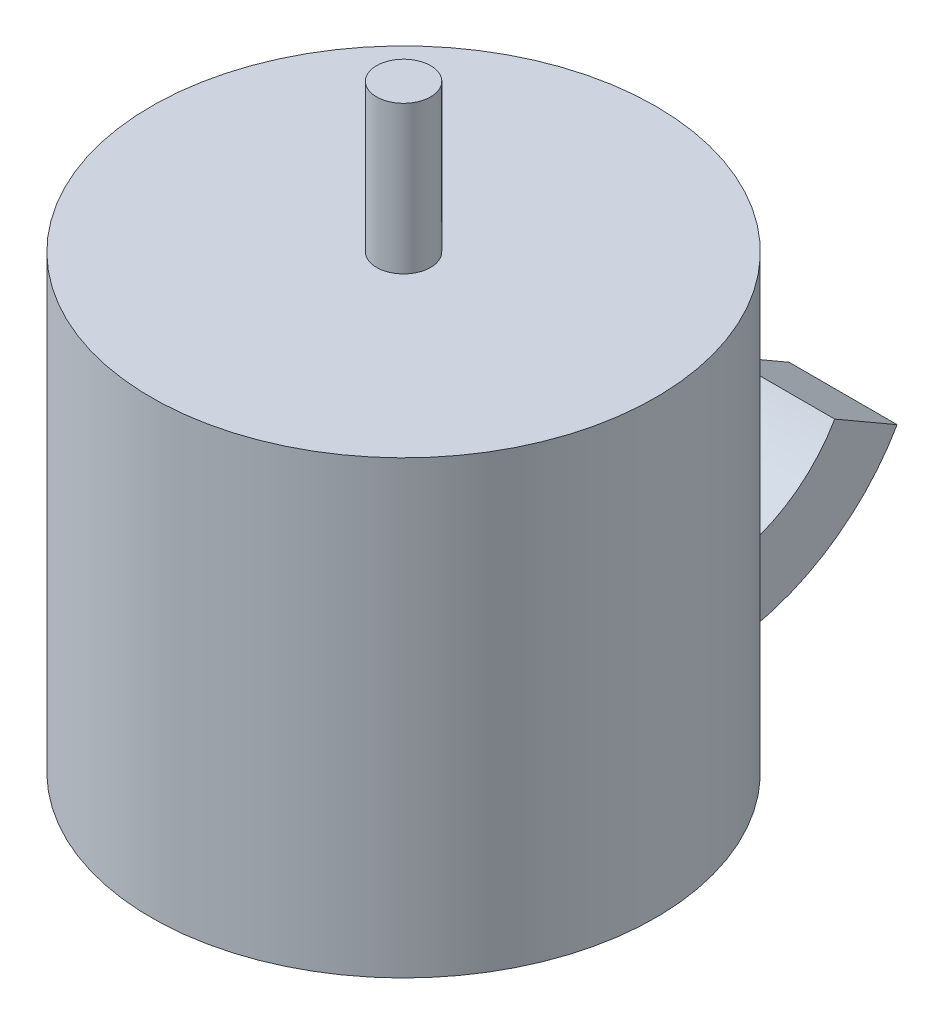
SolidWorks part; units mm, degrees
ref_plane "Front Plane" through (0, 0, 0) normal (0, 0, 1) x (1, 0, 0)
ref_plane "Top Plane" through (0, 0, 0) normal (0, 1, 0) x (1, 0, 0)
ref_plane "Right Plane" through (0, 0, 0) normal (1, 0, 0) x (0, 0, -1)
sketch "Sketch1" plane through (0, 0, 0) normal (0, 0, 1) x (1, 0, 0)
  line L0 (0, -74.46) -> (0, 71.5861) construction
  line L1 (-0.75, 0) -> (-7, 0)
  line L2 (55, 0) -> (-55, 0) construction
  line L3 (-7, 0) -> (-7, 12.5)
  line L4 (-7, 12.5) -> (-0.75, 12.5)
  line L5 (0, -0.9) -> (0, 16.6)
  line L6 (-0.75, 0) -> (-0.75, -0.9)
  line L7 (-0.75, 12.5) -> (-0.75, 16.6)
  line L8 (-0.75, 16.6) -> (0, 16.6)
  line L9 (-0.75, -0.9) -> (0, -0.9)
  dimension "D1" = 7
  dimension "D2" = 0.75
  dimension "D3" = 12.5
  dimension "D4" = 4.1
  dimension "D5" = 17.5
revolve "Revolve1" add sketch "Sketch1" angle 360 about L0
hole_wizard "M2x0.4 Tapped Hole1" positions "Sketch2" profile "Sketch3" tap size "M2x0.4" standard "ANSI Metric"
sketch "Sketch2" plane through (0, 0, 0) normal (0, -1, 0) x (-1, 0, 0)
  line L1 (-3.182, -3.182) -> (0, 0) construction
  line L2 (0, 0) -> (0, -2.9249) construction
  circle A0 centre (0, 0) radius 4.5
  point P0 (3.182, -3.182)
  point P11 (-3.182, -3.182)
  point P12 (-3.182, 3.182)
  point P13 (3.182, 3.182)
  dimension "D2" = 9
  dimension "D3" = 45
  dimension "D1" = 4
sketch "Sketch3" plane through (-3.182, 0, 3.182) normal (1, 0, 0) x (0, 0, -1)
  line L0 (0, 0) -> (0, 5.6807)
  line L1 (0, 5.6807) -> (0.8, 5.2)
  line L2 (0.8, 5.2) -> (0.8, 0)
  line L5 (0.8, 0) -> (0, 0)
  line L10 (0, 5.6807) -> (-0.8, 5.2) construction
  line L11 (0, -6.35) -> (0, 107.95) construction
  dimension "Tap Drill Dia." = 1.6
  dimension "Tap Drill Depth" = 5.2
  dimension "Drill Angle" = 118
cosmetic thread "Hole Thread1" parameters "D1"=4, "D2"=2
cosmetic thread "Hole Thread3" parameters "D1"=4, "D2"=2
cosmetic thread "Hole Thread4" parameters "D1"=4, "D2"=2
cosmetic thread "Hole Thread5" parameters "D1"=4, "D2"=2
ref_plane "Plane1" through (0, 0, -7) normal (0, 0, -1) x (-1, 0, 0)
sketch "Sketch4" plane through (0, 0, -7) normal (0, 0, -1) x (-1, 0, 0)
  line L1 (1.5, 0) -> (-1.5, 0)
  line L2 (1.5, 0) -> (1.5, 2)
  line L3 (1.5, 2) -> (-1.5, 2)
  line L4 (-1.5, 0) -> (-1.5, 2)
  point P4 (0, 0)
  dimension "D1" = 3
  dimension "D2" = 2
extrude "Boss-Extrude1" [suppressed] add sketch "Sketch4" along normal blind 10 and the other way blind 2
sketch "Sketch7" plane through (0, 0, -7) normal (0, 0, -1) x (-1, 0, 0)
  line L1 (1.5, 0) -> (-1.5, 0)
  line L2 (1.5, 0) -> (1.5, 2)
  line L3 (1.5, 2) -> (-1.5, 2)
  line L4 (-1.5, 0) -> (-1.5, 2)
  line L5 (7, 6) -> (-7, 6) construction
  point P4 (0, 0)
  dimension "D1" = 2
  dimension "D2" = 3
  dimension "D3" = 4
revolve "Revolve3" add sketch "Sketch7" angle 60 about L5 other way angle 10
